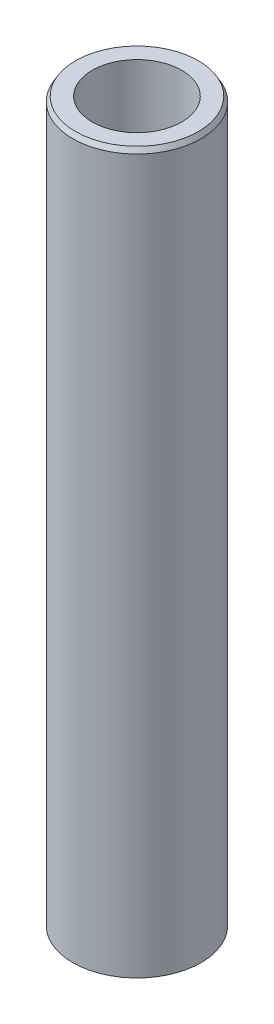
SolidWorks part; units mm, degrees
ref_plane "Front Plane" through (0, 0, 0) normal (0, 0, 1) x (1, 0, 0)
ref_plane "Top Plane" through (0, 0, 0) normal (0, 1, 0) x (1, 0, 0)
ref_plane "Right Plane" through (0, 0, 0) normal (1, 0, 0) x (0, 0, -1)
sketch "Sketch1" plane through (0, 0, 0) normal (0, 1, 0) x (1, 0, 0)
  circle A0 centre (0, 0) radius 47.5
  dimension "SHAFT_OD" = 95
extrude "Boss-Extrude1" add sketch "Sketch1" along normal blind 533.7255
sketch "Sketch2" plane through (0, 0, 0) normal (0, 1, 0) x (1, 0, 0)
  circle A0 centre (0, 0) radius 33.158
  dimension "BORE_D" = 66.316
extrude "Cut-Extrude1" cut sketch "Sketch2" along normal through all
chamfer "Chamfer1" distance 3.5517 angle 30 2 edges at (0, 533.7255, 47.5) (0, 0, 47.5) first distance on face at (0, 533.7255, 47.5) first distance on face at (0, 0, 33.158)
